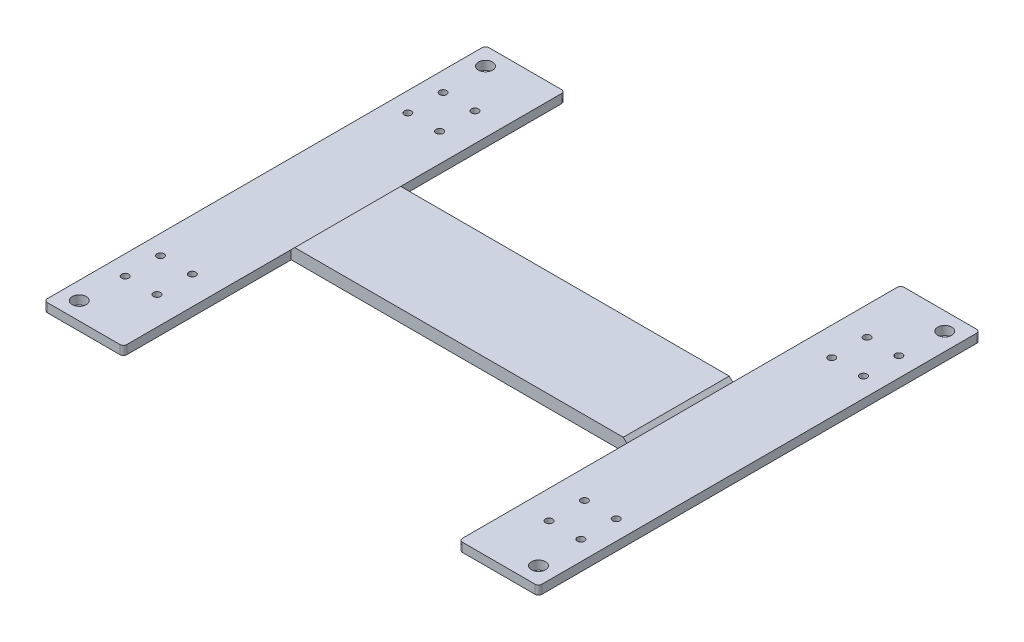
SolidWorks part; units mm, degrees
material "1060 Alloy"
ref_plane "Front (XY)" through (0, 0, 0) normal (0, 0, 1) x (1, 0, 0)
ref_plane "Top (XZ)" through (0, 0, 0) normal (0, 1, 0) x (1, 0, 0)
ref_plane "Right (YZ)" through (0, 0, 0) normal (1, 0, 0) x (0, 0, -1)
sketch "Sketch1" plane through (0, 0, 0) normal (0, 1, 0) x (1, 0, 0)
  line L0 (-140, 125) -> (-140, -125)
  line L1 (-140, -125) -> (-95, -125)
  line L2 (-95, -125) -> (-95, 125)
  line L3 (-95, 125) -> (-140, 125)
  line L4 (0, 0) -> (0, -20.8307) construction
  line L5 (95, 125) -> (140, 125)
  line L6 (95, -125) -> (95, 125)
  line L7 (140, -125) -> (95, -125)
  line L8 (140, 125) -> (140, -125)
  point P4 (-140, 0)
  dimension "D1" = 45
  dimension "D2" = 250
  dimension "D3" = 140
extrude "Boss-Extrude1" add sketch "Sketch1" along normal blind 5
sketch "Sketch2" plane through (0, 0, 0) normal (0, 1, 0) x (1, 0, 0)
  line L0 (95, 125) -> (95, -125) construction
  line L1 (-95, -125) -> (-95, 125) construction
  line L2 (95, 30) -> (95, -30)
  line L3 (-95, -30) -> (-95, 30)
  line L4 (-95, 30) -> (95, 30)
  line L5 (95, -30) -> (-95, -30)
  point P8 (0, 30)
  dimension "D1" = 60
  dimension "D2" = 30
extrude "Boss-Extrude2" add sketch "Sketch2" along normal blind 7
chamfer "Chamfer1" distance 2 angle 45 2 edges at (95, 7, 0) (-95, 7, 0)
fillet "Fillet1" radius 2 8 edges at (140, 2.5, -125) (95, 2.5, -125) (95, 2.5, 125) (140, 2.5, 125) (-95, 2.5, 125) (-140, 2.5, 125) (-95, 2.5, -125) (-140, 2.5, -125)
sketch "Sketch3" plane through (0, 5, 0) normal (0, 1, 0) x (1, 0, 0)
  line L0 (0, 0) -> (-29.1594, 0) construction
  circle A0 centre (-129, 90) radius 2
  circle A1 centre (-111, 90) radius 2
  circle A2 centre (-129, 70) radius 2
  circle A3 centre (-111, 70) radius 2
  dimension "D1" = 4
  dimension "D2" = 129
  dimension "D3" = 18
  dimension "D4" = 20
  dimension "D5" = 70
extrude "Cut-Extrude1" cut sketch "Sketch3" against normal through all
pattern_linear "LPattern1" count 2 spacing 240 along (1, 0, 0) count 2 spacing 160 along (0, 0, 1) of "Cut-Extrude1"
sketch "Sketch4" plane through (0, 5, 0) normal (0, 1, 0) x (1, 0, 0)
  line L0 (-97, 125) -> (-138, 125) construction
  line L1 (-140, 123) -> (-140, -123) construction
  circle A0 centre (-130, 115) radius 4
  dimension "D1" = 8
  dimension "D2" = 10
  dimension "D3" = 10
extrude "Cut-Extrude2" cut sketch "Sketch4" against normal through all
pattern_linear "LPattern2" count 2 spacing 260 along (1, 0, 0) count 2 spacing 230 along (0, 0, 1) of "Cut-Extrude2"
